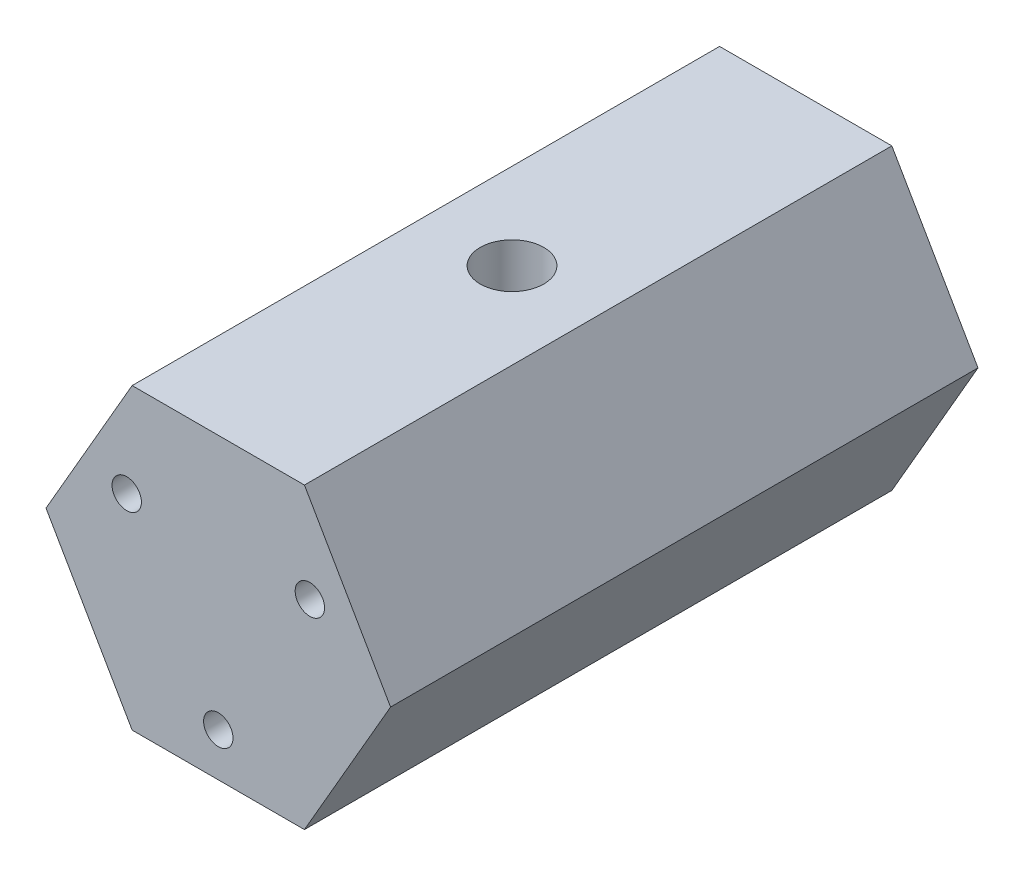
SolidWorks part; units mm, degrees
material "6061-T6 (SS)"
ref_plane "Front Plane" through (0, 0, 0) normal (0, 0, 1) x (1, 0, 0)
ref_plane "Top Plane" through (0, 0, 0) normal (0, 1, 0) x (1, 0, 0)
ref_plane "Right Plane" through (0, 0, 0) normal (1, 0, 0) x (0, 0, -1)
sketch "Sketch1" plane through (0, 0, 0) normal (0, 0, 1) x (1, 0, 0)
  line L7 (-7.3323, -12.7) -> (7.3323, -12.7)
  line L8 (7.3323, -12.7) -> (14.6647, 0)
  line L9 (14.6647, 0) -> (7.3323, 12.7)
  line L10 (7.3323, 12.7) -> (-7.3323, 12.7)
  line L11 (-7.3323, 12.7) -> (-14.6647, 0)
  line L12 (-14.6647, 0) -> (-7.3323, -12.7)
  circle A0 centre (0, 0) radius 9 construction
  circle A1 centre (-7.7942, 4.5) radius 1.25
  circle A2 centre (7.7942, 4.5) radius 1.25
  circle A3 centre (0, -9) radius 1.25
  circle A4 centre (0, 0) radius 12.7 construction
  circle A12 centre (0, 0) radius 9 construction
  point P11 (0, 0)
  point P23 (14.6647, 0)
  dimension "D1" = 3
  dimension "D2" = 2.5
  dimension "D3" = 25.4
extrude "Boss-Extrude1" add sketch "Sketch1" along normal blind 50
sketch "Sketch3" plane through (0, 12.7, 0) normal (0, 1, 0) x (1, 0, 0)
  line L0 (0, 0) -> (0, -50) construction
  line L1 (7.3323, -50) -> (-7.3323, -50) construction
  point P0 (0, -25)
hole_wizard "1/4-28 Tapped Hole1" positions "Sketch3" profile "Sketch4" tap size "1/4-28" standard "ANSI Inch" end condition through all
cosmetic thread "Hole Thread1" parameters "D2"=6.35
sketch "Sketch4" plane through (0, 12.7, 25) normal (1, 0, 0) x (0, 0, 1)
  line L0 (0, 0) -> (0, 25.4)
  line L1 (0, 25.4) -> (2.7051, 25.4)
  line L2 (2.7051, 25.4) -> (2.7051, 0)
  line L5 (2.7051, 0) -> (0, 0)
  line L11 (0, -6.35) -> (0, 107.95) construction
  dimension "Thru Tap Drill Dia." = 5.4102
  dimension "Thru Tap Drill Depth" = 25.4
equation "\"D1@Boss-Extrude1\"=\"Strut Length@Rocker Bogie Assy.Assembly\""
